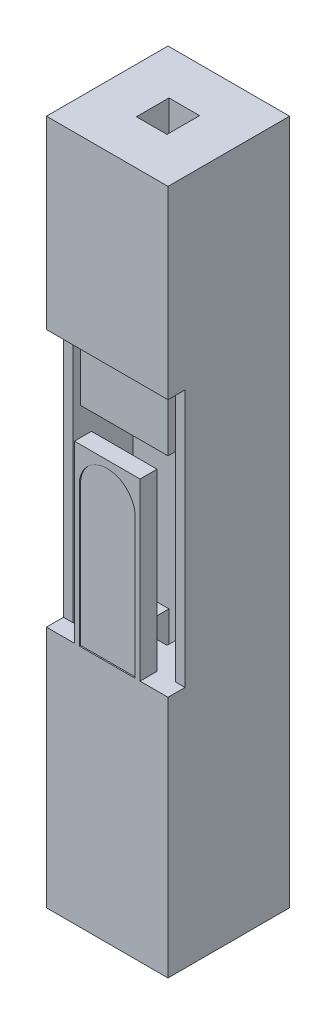
SolidWorks part; units mm, degrees
other "Camera1"
material "Nylon 101"
ref_plane "Front Plane" through (0, 0, 0) normal (0, 0, 1) x (1, 0, 0)
ref_plane "Top Plane" through (0, 0, 0) normal (0, 1, 0) x (1, 0, 0)
ref_plane "Right Plane" through (0, 0, 0) normal (1, 0, 0) x (0, 0, -1)
sketch "Sketch2" plane through (0, 0, 0) normal (0, 1, 0) x (1, 0, 0)
  line L1 (-1.25, -1.25) -> (1.25, -1.25)
  line L2 (-1.25, -1.25) -> (-1.25, 1.25)
  line L3 (-1.25, 1.25) -> (1.25, 1.25)
  line L4 (1.25, -1.25) -> (1.25, 1.25)
  line L5 (-1.25, -1.25) -> (1.25, 1.25) construction
  line L6 (-1.25, 1.25) -> (1.25, -1.25) construction
  point P0 (0, 0)
  dimension "D1" = 2.5
extrude "Boss-Extrude1" add sketch "Sketch2" along normal mid plane 14.1
sketch "Sketch3" plane through (0, 7.05, 0) normal (0, 1, 0) x (1, 0, 0)
  line L1 (0.315, -0.335) -> (-0.315, -0.335)
  line L2 (0.315, -0.335) -> (0.315, 0.335)
  line L3 (0.315, 0.335) -> (-0.315, 0.335)
  line L4 (-0.315, -0.335) -> (-0.315, 0.335)
  line L5 (0.315, -0.335) -> (-0.315, 0.335) construction
  line L6 (0.315, 0.335) -> (-0.315, -0.335) construction
  point P0 (0, 0)
  dimension "D1" = 0.67
  dimension "D2" = 0.63
extrude "Pinhole" cut sketch "Sketch3" against normal up to next
sketch "Sketch4" plane through (0, 0, 1.25) normal (0, 0, 1) x (1, 0, 0)
  line L0 (-1.25, 7.05) -> (-1.25, -7.05) construction
  line L1 (-1.25, 3.25) -> (1.25, 3.25)
  line L2 (-1.25, 3.25) -> (-1.25, -2.05)
  line L3 (-1.25, -2.05) -> (-0.675, -2.05)
  line L4 (1.25, 3.25) -> (1.25, -2.05)
  line L5 (0.675, -2.05) -> (1.25, -2.05)
  line L6 (-0.675, -2.05) -> (0.675, -2.05) construction
  line L7 (1.25, 7.05) -> (1.25, -7.05) construction
  line L8 (-1.25, 7.05) -> (1.25, 7.05) construction
  line L9 (-1.25, -7.05) -> (1.25, -7.05) construction
  line L10 (-0.675, -2.05) -> (-0.675, 1.55)
  line L11 (-0.675, 1.55) -> (0.675, 1.55)
  line L12 (0.675, -2.05) -> (0.675, 1.55)
  dimension "D1" = 3.8
  dimension "D2" = 5
  dimension "D3" = 1.35
  dimension "D4" = 3.6
extrude "Cut-Extrude2" cut sketch "Sketch4" against normal blind 0.35
sketch "Sketch5" plane through (0, 0, 0.9) normal (0, 0, 1) x (1, 0, 0)
  line L0 (-1.25, 7.05) -> (1.25, 7.05) construction
  line L1 (-1.05, 3.25) -> (1.05, 3.25)
  line L2 (-1.05, 3.25) -> (-1.05, -2.05)
  line L3 (-1.05, -2.05) -> (1.05, -2.05)
  line L4 (1.05, 3.25) -> (1.05, -2.05)
  line L5 (-1.05, 3.25) -> (1.05, -2.05) construction
  line L6 (-1.05, -2.05) -> (1.05, 3.25) construction
  line L7 (0.675, -2.05) -> (1.25, -2.05) construction
  line L8 (-1.25, 3.25) -> (-1.25, -2.05) construction
  line L9 (1.25, 3.25) -> (-1.25, 3.25) construction
  point P4 (0, 0.6)
  point P5 (0, 3.25)
  point P8 (0, 7.05)
  dimension "D1" = 0.2
extrude "Cut-Extrude3" cut sketch "Sketch5" against normal up to surface (1.235 mm away) up to face at (0, 0, -0.335)
sketch "Sketch6" plane through (0, 0, 1.25) normal (0, 0, 1) x (1, 0, 0)
  line L0 (-0.575, -2.05) -> (-0.575, 0.825)
  line L1 (-0.675, -2.05) -> (-0.675, 1.55) construction
  line L2 (-0.6825, -2.05) -> (0.6825, -2.05)
  line L3 (-1.05, -2.05) -> (-0.315, -2.05) construction
  line L4 (0.315, -2.05) -> (1.05, -2.05) construction
  line L5 (0, 1.55) -> (0, -2.05) construction
  line L6 (-0.675, 1.55) -> (0.675, 1.55) construction
  line L7 (0.575, -2.05) -> (0.575, 0.825)
  arc A0 (-0.575, 0.825) -> (0.575, 0.825) centre (0, 0.825) cw
  point P17 (0, 1.4)
  dimension "D2" = 0.15
  dimension "D1" = 0.1
extrude "Cut-Extrude5" cut sketch "Sketch6" against normal blind 0.025 contours L5 A0 L0 L2 | A0 L5 L2 L7 region at (-0.2816, -0.3842, 1.25) region at (0.2816, -0.3842, 1.25)
sketch "Sketch7" plane through (0, -7.05, 0) normal (0, -1, 0) x (1, 0, 0)
  line L0 (-1.25, -1.25) -> (-1.25, 1.25) construction
  line L1 (1.05, -1.05) -> (-1.05, -1.05)
  line L2 (1.05, -1.05) -> (1.05, 1.05)
  line L3 (1.05, 1.05) -> (-1.05, 1.05)
  line L4 (-1.05, -1.05) -> (-1.05, 1.05)
  line L5 (1.05, -1.05) -> (-1.05, 1.05) construction
  line L6 (1.05, 1.05) -> (-1.05, -1.05) construction
  point P0 (0, 0)
  dimension "D1" = 0.2
extrude "Cut-Extrude6" cut sketch "Sketch7" against normal blind 4
sketch "Sketch8" [suppressed] plane through (0, -3.05, 0) normal (0, -1, 0) x (1, 0, 0)
  circle A0 centre (0, 0) radius 0.45
  circle A1 centre (0, 0) radius 0.55
  dimension "D1" = 0.9
  dimension "D2" = 0.1
extrude "Wire hole" [suppressed] add sketch "Sketch8" along normal blind 3
sketch "Sketch9" plane through (0, 0, -0.335) normal (0, 0, 1) x (1, 0, 0)
  line L1 (-0.9, 2.9) -> (-0.75, 2.9)
  line L2 (-0.9, 2.9) -> (-0.9, 1.9)
  line L3 (-0.9, 1.9) -> (-0.75, 1.9)
  line L4 (0.9, 2.9) -> (0.9, 1.9)
  line L5 (0.75, 2.9) -> (-0.75, 2.9) construction
  line L6 (0.9, 2.9) -> (0.75, 2.9)
  line L7 (-0.315, 3.25) -> (0.315, 3.25) construction
  line L8 (-0.75, 2.9) -> (-0.75, 1.9)
  line L9 (0, 2.9) -> (0, 1.9) construction
  line L10 (0.75, 2.9) -> (0.75, 1.9)
  line L11 (-1.05, 3.25) -> (-1.05, -2.05) construction
  line L12 (0, 3.25) -> (0, 2.9) construction
  line L13 (0.75, 1.9) -> (-0.75, 1.9) construction
  line L14 (0.75, 1.9) -> (0.9, 1.9)
  point P4 (0, 2.4)
  point P23 (0, 2.9)
  point P24 (0, 1.9)
  dimension "D1" = 1
  dimension "D2" = 0.15
  dimension "D3" = 0.15
  dimension "D4" = 0.85
extrude "Holder-1" add sketch "Sketch9" along normal offset from surface (1.085 mm away) 0.15 up to face at (0, -0.25, 0.9)
sketch "Sketch10" plane through (0, 0, 0.75) normal (0, 0, 1) x (1, 0, 0)
  line L1 (-0.9, 2.9) -> (0.9, 2.9)
  line L2 (-0.9, 2.9) -> (-0.9, 1.9)
  line L3 (-0.9, 1.9) -> (0.9, 1.9)
  line L4 (0.9, 2.9) -> (0.9, 1.9)
  line L5 (-0.9, 2.9) -> (0.9, 1.9) construction
  line L6 (-0.9, 1.9) -> (0.9, 2.9) construction
  point P4 (0, 2.4)
extrude "Holder-2" add sketch "Sketch10" along normal blind 0.15
ref_plane "Snap plane" through (0, 6.05, 0) normal (0, 1, 0) x (1, 0, 0)
